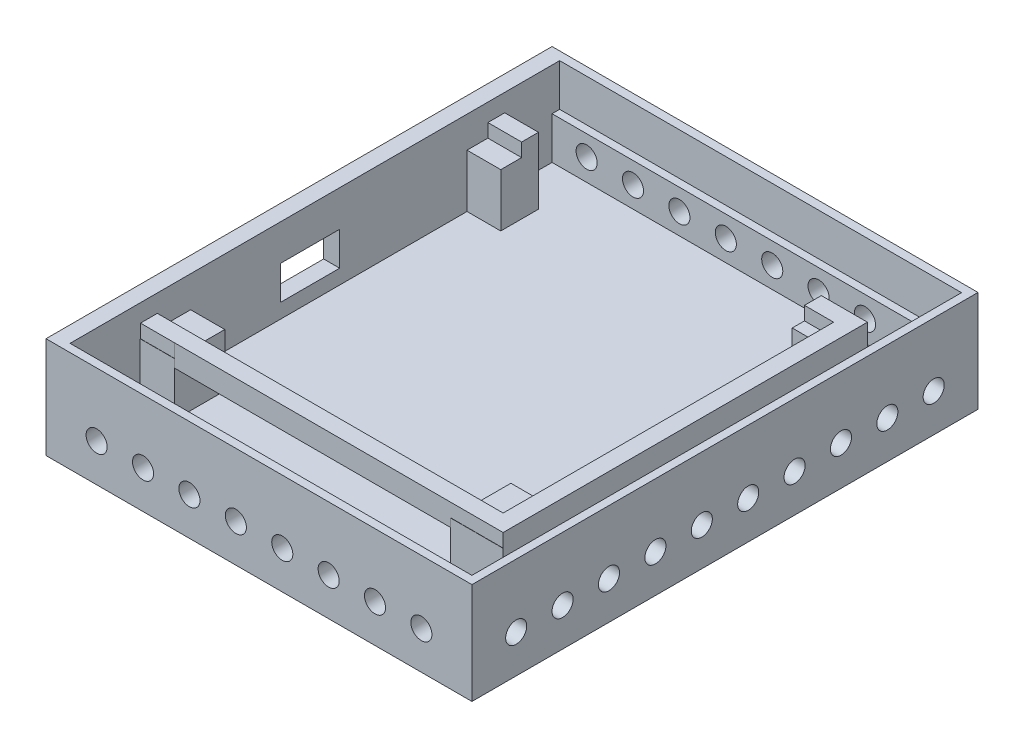
SolidWorks part; units mm, degrees
ref_plane "Piano frontale" through (0, 0, 0) normal (0, 0, 1) x (1, 0, 0)
ref_plane "Piano superiore" through (0, 0, 0) normal (0, 1, 0) x (1, 0, 0)
ref_plane "Piano destro" through (0, 0, 0) normal (1, 0, 0) x (0, 0, -1)
sketch "Schizzo1" plane through (0, 0, 0) normal (0, 1, 0) x (1, 0, 0)
  line L1 (0, 0) -> (50.5, 0)
  line L2 (0, 0) -> (0, 60)
  line L3 (0, 60) -> (50.5, 60)
  line L4 (50.5, 0) -> (50.5, 60)
  dimension "D1" = 60
  dimension "D2" = 50.5
extrude "Estrusione-Estrusione1" add sketch "Schizzo1" along normal blind 2
sketch "Schizzo2" plane through (0, 2, 0) normal (0, 1, 0) x (1, 0, 0)
  line L0 (0, 0) -> (50.5, 0) construction
  line L1 (0, 60) -> (1.9, 60)
  line L2 (0, 60) -> (0, 0)
  line L3 (0, 0) -> (1.9, 0)
  line L4 (1.9, 60) -> (1.9, 0)
  dimension "D1" = 1.9
extrude "Estrusione-Estrusione2" add sketch "Schizzo2" along normal blind 10
sketch "Schizzo3" plane through (0, 2, 0) normal (0, 1, 0) x (1, 0, 0)
  line L0 (50.5, 0) -> (50.5, 60) construction
  line L1 (1.9, 60) -> (50.5, 60)
  line L2 (1.9, 60) -> (1.9, 58.1)
  line L3 (1.9, 58.1) -> (50.5, 58.1)
  line L4 (50.5, 60) -> (50.5, 58.1)
  dimension "D1" = 1.9
extrude "Estrusione-Estrusione3" add sketch "Schizzo3" along normal blind 10
sketch "Schizzo4" plane through (0, 2, 0) normal (0, 1, 0) x (1, 0, 0)
  line L0 (1.9, 0) -> (50.5, 0) construction
  line L1 (50.5, 58.1) -> (48.6, 58.1)
  line L2 (50.5, 58.1) -> (50.5, 0)
  line L3 (50.5, 0) -> (48.6, 0)
  line L4 (48.6, 58.1) -> (48.6, 0)
  dimension "D1" = 1.9
extrude "Estrusione-Estrusione4" add sketch "Schizzo4" along normal blind 10
sketch "Schizzo5" plane through (0, 2, 0) normal (0, 1, 0) x (1, 0, 0)
  line L0 (48.6, 58.1) -> (48.6, 0) construction
  line L1 (1.9, 0) -> (48.6, 0)
  line L2 (1.9, 0) -> (1.9, 1.9)
  line L3 (1.9, 1.9) -> (48.6, 1.9)
  line L4 (48.6, 0) -> (48.6, 1.9)
  dimension "D1" = 1.9
extrude "Estrusione-Estrusione5" add sketch "Schizzo5" along normal blind 10
sketch "Schizzo8" plane through (0, 2, 0) normal (0, 1, 0) x (1, 0, 0)
  line L0 (1.9, 1.9) -> (1.9, 58.1) construction
  line L2 (1.9, 55.0174) -> (5.9, 55.0174)
  line L3 (1.9, 55.0174) -> (1.9, 48.0174)
  line L4 (1.9, 48.0174) -> (5.9, 48.0174)
  line L5 (5.9, 55.0174) -> (5.9, 48.0174)
  dimension "D1" = 4
  dimension "D2" = 7
extrude "Estrusione-Estrusione6" add sketch "Schizzo8" along normal blind 6.3
sketch "Schizzo13" plane through (0, 2, 0) normal (0, 1, 0) x (1, 0, 0)
  line L1 (39.4364, 55.0174) -> (45.2969, 55.0174)
  line L2 (39.4364, 55.0174) -> (39.4364, 49.0383)
  line L3 (39.4364, 49.0383) -> (45.2969, 49.0383)
  line L4 (45.2969, 55.0174) -> (45.2969, 49.0383)
extrude "Estrusione-Estrusione12" add sketch "Schizzo13" along normal blind 6.3
sketch "Schizzo14" plane through (0, 2, 0) normal (0, 1, 0) x (1, 0, 0)
  line L4 (45.2969, 16.4164) -> (38.6994, 16.4164)
  line L5 (45.2969, 16.4164) -> (45.2969, 9.2728)
  line L6 (45.2969, 9.2728) -> (38.6994, 9.2728)
  line L7 (38.6994, 16.4164) -> (38.6994, 9.2728)
extrude "Estrusione-Estrusione13" add sketch "Schizzo14" along normal blind 6.3
sketch "Schizzo15" plane through (0, 2, 0) normal (0, 1, 0) x (1, 0, 0)
  line L3 (1.9, 1.9) -> (1.9, 48.0174) construction
  line L5 (1.9, 9.2728) -> (5.9531, 9.2728)
  line L6 (1.9, 9.2728) -> (1.9, 15.2426)
  line L7 (1.9, 15.2426) -> (5.9531, 15.2426)
  line L8 (5.9531, 9.2728) -> (5.9531, 15.2426)
extrude "Estrusione-Estrusione14" add sketch "Schizzo15" along normal blind 6.3
sketch "Schizzo16" plane through (0, 8.3, 0) normal (0, 1, 0) x (1, 0, 0)
  line L0 (1.9, 55.0174) -> (1.9, 48.0174) construction
  line L1 (1.9, 50.4884) -> (5.9, 50.4884)
  line L2 (1.9, 50.4884) -> (1.9, 52.4884)
  line L3 (1.9, 52.4884) -> (5.9, 52.4884)
  line L4 (5.9, 50.4884) -> (5.9, 52.4884)
  line L5 (1.9, 50.4884) -> (18.7, 50.4884) construction
  line L6 (5.9, 48.0174) -> (5.9, 55.0174) construction
  dimension "D1" = 2
extrude "Estrusione-Estrusione15" add sketch "Schizzo16" along normal blind 1.6
sketch "Schizzo17" plane through (0, 8.3, 0) normal (0, 1, 0) x (1, 0, 0)
  line L0 (39.4364, 55.0174) -> (39.4364, 49.0383) construction
  line L1 (39.4364, 50.4884) -> (42.9, 50.4884)
  line L2 (39.4364, 50.4884) -> (39.4364, 52.4884)
  line L3 (39.4364, 52.4884) -> (42.9, 52.4884)
  line L4 (42.9, 50.4884) -> (42.9, 52.4884)
  line L5 (32.8, 50.4884) -> (42.9, 50.4884) construction
  dimension "D1" = 2
extrude "Estrusione-Estrusione16" add sketch "Schizzo17" along normal blind 1.6
sketch "Schizzo18" plane through (0, 8.3, 0) normal (0, 1, 0) x (1, 0, 0)
  line L0 (39.4364, 49.0383) -> (45.2969, 49.0383) construction
  line L1 (42.9, 49.0383) -> (44.9, 49.0383)
  line L2 (42.9, 49.0383) -> (42.9, 54.2995)
  line L3 (42.9, 54.2995) -> (44.9, 54.2995)
  line L4 (44.9, 49.0383) -> (44.9, 54.2995)
  line L5 (42.9, 50.4884) -> (42.9, 9.4884) construction
  dimension "D1" = 2
extrude "Estrusione-Estrusione17" add sketch "Schizzo18" along normal blind 1.6
sketch "Schizzo19" plane through (0, 8.3, 0) normal (0, 1, 0) x (1, 0, 0)
  line L1 (42.9, 50.4884) -> (42.9, 9.4884) construction
  line L2 (42.9, 16.4205) -> (44.9, 16.4205)
  line L3 (42.9, 16.4205) -> (42.9, 11.3005)
  line L4 (42.9, 11.3005) -> (44.9, 11.3005)
  line L5 (44.9, 16.4205) -> (44.9, 11.3005)
  dimension "D1" = 2
extrude "Estrusione-Estrusione18" add sketch "Schizzo19" along normal blind 1.6
sketch "Schizzo23" plane through (0, 8.3, 0) normal (0, 1, 0) x (1, 0, 0)
  line L0 (38.6994, 16.4164) -> (38.6994, 9.2728) construction
  line L1 (44.9, 11.3005) -> (38.6994, 11.3005)
  line L2 (44.9, 11.3005) -> (44.9, 9.3005)
  line L3 (44.9, 9.3005) -> (38.6994, 9.3005)
  line L4 (38.6994, 11.3005) -> (38.6994, 9.3005)
  dimension "D1" = 2
extrude "Estrusione-Estrusione19" add sketch "Schizzo23" along normal blind 1.6
sketch "Schizzo25" plane through (0, 8.3, 0) normal (0, 1, 0) x (1, 0, 0)
  line L0 (1.9, 15.2426) -> (1.9, 9.2728) construction
  line L1 (1.9, 11.2993) -> (5.9531, 11.2993)
  line L2 (1.9, 11.2993) -> (1.9, 9.2993)
  line L3 (1.9, 9.2993) -> (5.9531, 9.2993)
  line L4 (5.9531, 11.2993) -> (5.9531, 9.2993)
  line L5 (5.9531, 9.2728) -> (5.9531, 15.2426) construction
  dimension "D1" = 2
extrude "Estrusione-Estrusione20" add sketch "Schizzo25" along normal blind 1.6
sketch "Schizzo26" plane through (0, 8.3, 0) normal (0, 1, 0) x (1, 0, 0)
  line L0 (38.6994, 9.2728) -> (45.2969, 9.2728) construction
  line L1 (44.9, 16.4164) -> (45.2969, 16.4164)
  line L2 (44.9, 16.4164) -> (44.9, 9.2728)
  line L3 (44.9, 9.2728) -> (45.2969, 9.2728)
  line L4 (45.2969, 16.4164) -> (45.2969, 9.2728)
  line L5 (38.6994, 9.2728) -> (45.2969, 9.2728) construction
extrude "Taglio-Estrusione1" cut sketch "Schizzo26" against normal blind 6.3
sketch "Schizzo27" plane through (0, 8.3, 0) normal (0, 1, 0) x (1, 0, 0)
  line L1 (45.2969, 55.0174) -> (44.9, 55.0174)
  line L2 (45.2969, 55.0174) -> (45.2969, 49.0383)
  line L3 (45.2969, 49.0383) -> (44.9, 49.0383)
  line L4 (44.9, 55.0174) -> (44.9, 49.0383)
extrude "Taglio-Estrusione2" cut sketch "Schizzo27" against normal blind 6.3
sketch "Schizzo28" plane through (0, 8.3, 0) normal (0, 1, 0) x (1, 0, 0)
  line L1 (39.4364, 55.0174) -> (44.9, 55.0174)
  line L2 (39.4364, 55.0174) -> (39.4364, 54.2995)
  line L3 (39.4364, 54.2995) -> (44.9, 54.2995)
  line L4 (44.9, 55.0174) -> (44.9, 54.2995)
extrude "Taglio-Estrusione3" cut sketch "Schizzo28" against normal blind 6.3
sketch "Schizzo29" plane through (0, 8.3, 0) normal (0, 1, 0) x (1, 0, 0)
  line L1 (1.9, 55.0174) -> (5.9, 55.0174)
  line L2 (1.9, 55.0174) -> (1.9, 52.4884)
  line L3 (1.9, 52.4884) -> (5.9, 52.4884)
  line L4 (5.9, 55.0174) -> (5.9, 52.4884)
extrude "Taglio-Estrusione4" cut sketch "Schizzo29" against normal blind 6.3
sketch "Schizzo30" plane through (0, 0, -49.0383) normal (0, 0, 1) x (1, 0, 0)
  line L1 (44.9, 9.9) -> (42.9, 9.9)
  line L2 (44.9, 9.9) -> (44.9, 8.3)
  line L3 (44.9, 8.3) -> (42.9, 8.3)
  line L4 (42.9, 9.9) -> (42.9, 8.3)
extrude "Estrusione-Estrusione21" add sketch "Schizzo30" along normal blind 33.3
sketch "Schizzo31" plane through (38.6994, 0, 0) normal (-1, 0, 0) x (0, 0, 1)
  line L1 (-9.3005, 9.9) -> (-11.3005, 9.9)
  line L2 (-9.3005, 9.9) -> (-9.3005, 8.3)
  line L3 (-9.3005, 8.3) -> (-11.3005, 8.3)
  line L4 (-11.3005, 9.9) -> (-11.3005, 8.3)
extrude "Estrusione-Estrusione22" add sketch "Schizzo31" along normal blind 35
sketch "Schizzo32" plane through (0, 8.3, 0) normal (0, -1, 0) x (-1, 0, 0)
  line L0 (-5.9531, 11.3005) -> (-5.9531, 15.2426) construction
  line L1 (-38.6994, 9.3005) -> (-5.9531, 9.3005)
  line L2 (-38.6994, 9.3005) -> (-38.6994, 11.8326)
  line L3 (-38.6994, 11.8326) -> (-5.9531, 11.8326)
  line L4 (-5.9531, 9.3005) -> (-5.9531, 11.8326)
extrude "Estrusione-Estrusione23" add sketch "Schizzo32" along normal blind 1
sketch "Schizzo33" plane through (0, 8.3, 0) normal (0, -1, 0) x (-1, 0, 0)
  line L0 (-39.4364, 49.0383) -> (-42.9, 49.0383) construction
  line L1 (-44.9, 16.4164) -> (-42.588, 16.4164)
  line L2 (-44.9, 16.4164) -> (-44.9, 49.0383)
  line L3 (-44.9, 49.0383) -> (-42.588, 49.0383)
  line L4 (-42.588, 16.4164) -> (-42.588, 49.0383)
extrude "Estrusione-Estrusione24" add sketch "Schizzo33" along normal blind 1
sketch "Schizzo34" plane through (0, 0, 0) normal (-1, 0, 0) x (0, 0, 1)
  line L1 (-32.9188, 3.7296) -> (-25.9188, 3.7296)
  line L2 (-32.9188, 3.7296) -> (-32.9188, 7.7296)
  line L3 (-32.9188, 7.7296) -> (-25.9188, 7.7296)
  line L4 (-25.9188, 3.7296) -> (-25.9188, 7.7296)
  dimension "D1" = 4
  dimension "D2" = 7
extrude "Taglio-Estrusione5" cut sketch "Schizzo34" against normal blind 1.9
sketch "Schizzo35" plane through (0, 12, 0) normal (0, 1, 0) x (1, 0, 0)
  line L1 (48.6, 58.1) -> (49.55, 58.1)
  line L2 (48.6, 58.1) -> (48.6, 1.9)
  line L3 (48.6, 1.9) -> (49.55, 1.9)
  line L4 (49.55, 58.1) -> (49.55, 1.9)
  dimension "D1" = 0.95
extrude "Taglio-Estrusione6" cut sketch "Schizzo35" against normal blind 5
sketch "Schizzo36" plane through (0, 12, 0) normal (0, 1, 0) x (1, 0, 0)
  line L1 (49.55, 1.9) -> (1.9, 1.9)
  line L2 (49.55, 1.9) -> (49.55, 0.95)
  line L3 (49.55, 0.95) -> (1.9, 0.95)
  line L4 (1.9, 1.9) -> (1.9, 0.95)
  dimension "D1" = 0.95
  dimension "D2" = 47.65
extrude "Taglio-Estrusione7" cut sketch "Schizzo36" against normal blind 5
sketch "Schizzo38" plane through (0, 12, 0) normal (0, 1, 0) x (1, 0, 0)
  line L1 (49.55, 58.1) -> (1.9, 58.1)
  line L2 (49.55, 58.1) -> (49.55, 59)
  line L3 (49.55, 59) -> (1.9, 59)
  line L4 (1.9, 58.1) -> (1.9, 59)
  dimension "D1" = 47.65
  dimension "D2" = 0.9
extrude "Taglio-Estrusione8" cut sketch "Schizzo38" against normal blind 5
sketch "Schizzo39" plane through (0, 9.9, 0) normal (0, 1, 0) x (1, 0, 0)
  line L1 (44.9, 54.2995) -> (39.4364, 54.2995)
  line L2 (44.9, 54.2995) -> (44.9, 52.4884)
  line L3 (44.9, 52.4884) -> (39.4364, 52.4884)
  line L4 (39.4364, 54.2995) -> (39.4364, 52.4884)
extrude "Taglio-Estrusione9" cut sketch "Schizzo39" against normal blind 7.9
sketch "Schizzo40" plane through (48.6, 0, 0) normal (-1, 0, 0) x (0, 0, 1)
  circle A0 centre (-54.7483, 4.5) radius 1.25
  circle A1 centre (-49.2512, 4.5) radius 1.25
  circle A2 centre (-43.7556, 4.6606) radius 1.25
  circle A3 centre (-38.2565, 4.5) radius 1.25
  circle A4 centre (-32.757, 4.5) radius 1.25
  circle A5 centre (-27.2531, 4.5) radius 1.25
  circle A6 centre (-21.7531, 4.5) radius 1.25
  circle A7 centre (-16.2494, 4.5) radius 1.25
  circle A8 centre (-10.7495, 4.5) radius 1.25
  circle A9 centre (-5.248, 4.5) radius 1.25
  dimension "D1" = 2.5
  dimension "D2" = 2.5
  dimension "D3" = 2.5
  dimension "D4" = 2.5
  dimension "D5" = 2.5
  dimension "D6" = 2.5
  dimension "D7" = 2.5
  dimension "D8" = 2.5
  dimension "D9" = 2.5
  dimension "D10" = 2.5
extrude "Taglio-Estrusione10" cut sketch "Schizzo40" against normal blind 2
sketch "Schizzo41" plane through (0, 0, -1.9) normal (0, 0, -1) x (-1, 0, 0)
  circle A0 centre (-44.5052, 4.5) radius 1.25
  circle A1 centre (-39.0085, 4.5) radius 1.25
  circle A2 centre (-33.5128, 4.5) radius 1.25
  circle A3 centre (-28.0115, 4.5) radius 1.25
  circle A4 centre (-22.51, 4.5) radius 1.25
  circle A5 centre (-17.0056, 4.5) radius 1.25
  circle A6 centre (-11.5055, 4.5) radius 1.25
  circle A7 centre (-6.0035, 4.5) radius 1.25
  dimension "D1" = 2.5
  dimension "D2" = 2.5
  dimension "D3" = 2.5
  dimension "D4" = 2.5
  dimension "D5" = 2.5
  dimension "D6" = 2.5
  dimension "D7" = 2.5
  dimension "D8" = 2.5
extrude "Taglio-Estrusione11" cut sketch "Schizzo41" against normal blind 2
sketch "Schizzo42" plane through (0, 0, -58.1) normal (0, 0, 1) x (1, 0, 0)
  circle A0 centre (44.5052, 4.6041) radius 1.25
  circle A1 centre (39.0037, 4.5) radius 1.25
  circle A2 centre (33.5008, 4.5) radius 1.25
  circle A3 centre (28.0045, 4.5) radius 1.25
  circle A4 centre (22.5007, 4.5) radius 1.25
  circle A5 centre (16.9973, 4.5) radius 1.25
  circle A6 centre (11.4986, 4.5) radius 1.25
  circle A7 centre (5.998, 4.6041) radius 1.25
  dimension "D1" = 2.5
  dimension "D2" = 2.5
  dimension "D3" = 2.5
  dimension "D4" = 2.5
  dimension "D5" = 2.5
  dimension "D6" = 2.5
  dimension "D7" = 2.5
  dimension "D8" = 2.5
extrude "Taglio-Estrusione12" cut sketch "Schizzo42" against normal blind 2
